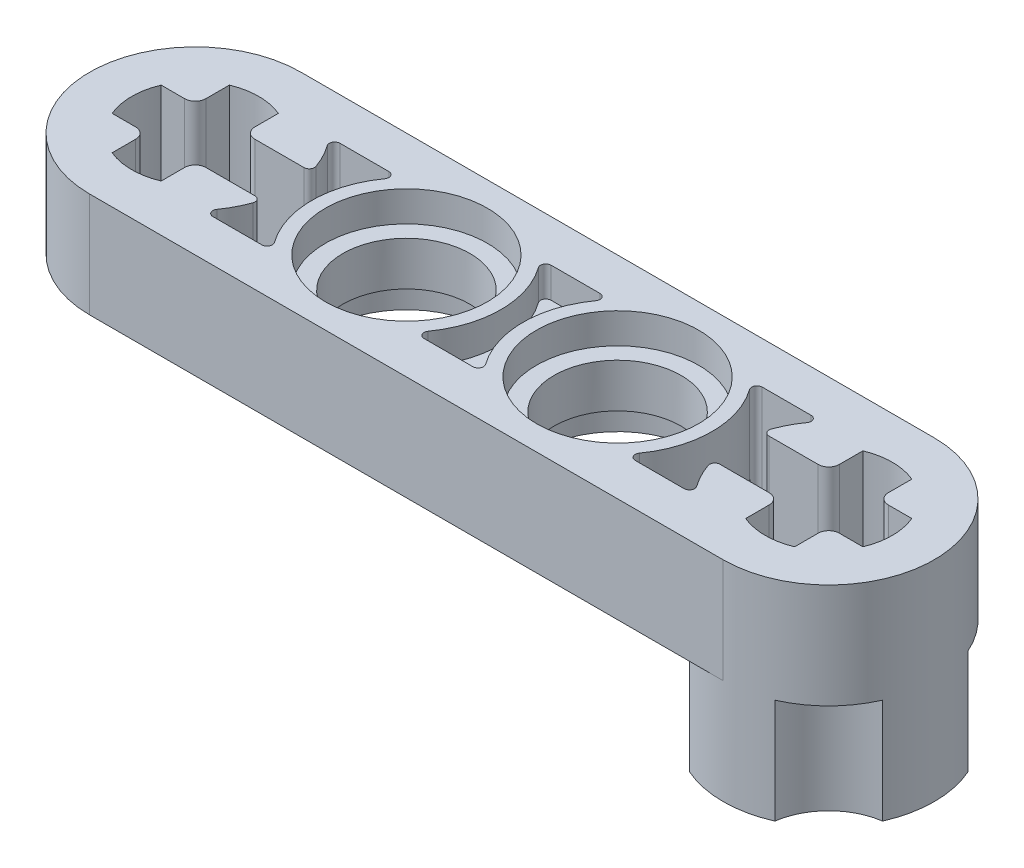
SolidWorks part; units mm, degrees
ref_plane "Front" through (0, 0, 0) normal (0, 0, 1) x (1, 0, 0)
ref_plane "Top" through (0, 0, 0) normal (0, 1, 0) x (1, 0, 0)
ref_plane "Right" through (0, 0, 0) normal (1, 0, 0) x (0, 0, -1)
sketch "Sketch1" plane through (0, 0, 0) normal (0, 1, 0) x (1, 0, 0)
  line L0 (0, 0) -> (0, 8.6394) construction
  line L1 (-11.9063, 3.9687) -> (11.9063, 3.9687)
  line L2 (11.9063, -3.9687) -> (-11.9063, -3.9687)
  line L3 (0, 0) -> (18.7139, 0) construction
  arc A0 (11.9063, 3.9687) -> (11.9063, -3.9687) centre (11.9063, 0) cw
  arc A1 (-11.9063, 3.9687) -> (-11.9063, -3.9687) centre (-11.9063, 0) ccw
  point P6 (0, 3.9687)
  point P11 (0, -3.9688)
  dimension "D1" = 7.9375
  dimension "D2" = 31.75
extrude "Base-Extrude" add sketch "Sketch1" along normal mid plane 3.937
sketch "Sketch2" plane through (0, 1.9685, 0) normal (0, 1, 0) x (-1, 0, 0)
  circle A0 centre (3.9688, 0) radius 2.3876
  dimension "D1" = 4.7752
  dimension "D2" = 3.9688
extrude "Cut-Extrude1" cut sketch "Sketch2" against normal through all
sketch "Sketch3" plane through (0, 1.9685, 0) normal (0, 1, 0) x (-1, 0, 0)
  circle A0 centre (3.9688, 0) radius 3.048
  dimension "D1" = 6.096
extrude "Cut-Extrude2" cut sketch "Sketch3" against normal blind 1.143
sketch "Sketch4" plane through (0, -1.9685, 0) normal (0, -1, 0) x (1, 0, 0)
  circle A0 centre (-3.9688, 0) radius 3.048
  dimension "D1" = 6.096
extrude "Cut-Extrude3" cut sketch "Sketch4" against normal blind 1.143
pattern_linear "LPattern1" count 2 spacing 7.9375 along (1, 0, 0) of "Cut-Extrude3", "Cut-Extrude2", "Cut-Extrude1"
sketch "Sketch5" plane through (0, 1.9685, 0) normal (0, 1, 0) x (-1, 0, 0)
  line L0 (11.9063, 0) -> (11.9063, -5.3472) construction
  line L1 (11.9063, 0) -> (8.2567, 0) construction
  line L2 (10.9855, -2.2029) -> (10.9855, -0.9207)
  line L3 (10.9855, -0.9207) -> (9.7033, -0.9207)
  line L4 (10.9855, 0.9208) -> (9.7033, 0.9208)
  line L5 (10.9855, 2.2029) -> (10.9855, 0.9208)
  line L6 (12.827, 2.2029) -> (12.827, 0.9208)
  line L7 (12.827, 0.9208) -> (14.1092, 0.9208)
  line L8 (12.827, -0.9207) -> (14.1092, -0.9207)
  line L9 (12.827, -2.2029) -> (12.827, -0.9207)
  arc A0 (10.9855, -2.2029) -> (12.827, -2.2029) centre (11.9063, 0) ccw
  arc A1 (9.7033, 0.9208) -> (9.7033, -0.9207) centre (11.9063, 0) ccw
  arc A2 (12.827, 2.2029) -> (10.9855, 2.2029) centre (11.9063, 0) ccw
  arc A3 (14.1092, -0.9207) -> (14.1092, 0.9208) centre (11.9063, 0) ccw
  dimension "D1" = 4.7752
  dimension "D2" = 0.9207
extrude "Cut-Extrude4" cut sketch "Sketch5" against normal through all
fillet "Fillet1" radius 0.3969 4 edges at (-12.827, 0, -0.9207) (-10.9855, 0, -0.9207) (-12.827, 0, 0.9208) (-10.9855, 0, 0.9208)
sketch "Sketch6" plane through (0, 1.9685, 0) normal (0, 1, 0) x (-1, 0, 0)
  line L0 (9.271, -2.3876) -> (6.604, -2.3876)
  line L1 (11.9063, 0) -> (3.9688, 0) construction
  line L2 (9.271, 2.3876) -> (6.604, 2.3876)
  line L3 (9.7033, -0.9207) -> (8.4715, -0.9207)
  line L4 (9.7033, 0.9208) -> (8.4715, 0.9208)
  circle A0 centre (3.9688, 0) radius 2.3876 construction
  arc A2 (6.604, -2.3876) -> (6.604, 2.3876) centre (3.9688, 0) ccw
  arc A3 (9.271, 2.3876) -> (8.4715, 0.9208) centre (11.9063, 0) ccw
  arc A4 (9.7033, 0.9208) -> (9.7033, -0.9207) centre (11.9063, 0) ccw construction
  arc A5 (9.7033, 0.9208) -> (9.7033, -0.9207) centre (11.9063, 0) ccw
  arc A6 (8.4715, -0.9207) -> (9.271, -2.3876) centre (11.9063, 0) ccw
  dimension "D2" = 7.112
extrude "Cut-Extrude5" cut sketch "Sketch6" against normal through all
fillet "Fillet2" radius 0.1984 6 edges at (-6.604, 0, -2.3876) (-9.271, 0, 2.3876) (-6.604, 0, 2.3876) (-9.271, 0, -2.3876) (-8.4715, 0, -0.9207) (-8.4715, 0, 0.9208)
mirror "Mirror1" about plane through (0, 0, 0) normal (1, 0, 0) of "Fillet2", "Cut-Extrude5", "Fillet1", "Cut-Extrude4"
sketch "Sketch7" plane through (7.6266, 1.9685, -1.7506) normal (0, 1, 0) x (-1, 0, 0)
  line L0 (8.9601, -0.637) -> (6.2931, -0.637)
  line L1 (11.5954, 1.7506) -> (3.6579, 1.7506) construction
  line L2 (8.9601, 4.1382) -> (6.2931, 4.1382)
  circle A0 centre (11.5954, 1.7506) radius 2.3876 construction
  circle A1 centre (3.6579, 1.7506) radius 2.3876 construction
  arc A2 (6.2931, -0.637) -> (6.2931, 4.1382) centre (3.6579, 1.7506) ccw
  arc A3 (8.9601, 4.1382) -> (8.0394, 1.7506) centre (11.5954, 1.7506) ccw
  arc A6 (8.0394, 1.7506) -> (8.9601, -0.637) centre (11.5954, 1.7506) ccw
  dimension "D2" = 7.112
extrude "Cut-Extrude6" cut sketch "Sketch7" against normal blind 1.143
fillet "Fillet3" radius 0.1984 4 edges at (-1.3335, 1.397, -2.3876) (1.3335, 1.397, -2.3876) (-1.3335, 1.397, 2.3876) (1.3335, 1.397, 2.3876)
mirror "Mirror2" about plane through (0, 0, 0) normal (0, 1, 0) of "Fillet3", "Cut-Extrude6"
sketch "Sketch8" plane through (0, -1.9685, 0) normal (0, -1, 0) x (1, 0, 0)
  circle A0 centre (11.9063, 0) radius 3.9687
  circle A1 centre (11.9063, 0) radius 2.3876
extrude "Boss-Extrude1" add sketch "Sketch8" along normal blind 3.937
sketch "Sketch9" plane through (0, -5.9055, 0) normal (0, -1, 0) x (1, 0, 0)
  line L0 (11.9063, 0) -> (11.9063, -4.7829) construction
  line L1 (11.9063, 0) -> (15.8424, -3.9361) construction
  circle A0 centre (15.875, -3.9687) radius 2.3876
  dimension "D2" = 4.7752
  dimension "D1" = 45
  dimension "D3" = 3.9688
extrude "Cut-Extrude7" cut sketch "Sketch9" against normal up to surface (3.937 mm away)
pattern_circular "CirPattern1" count 4 every 90 about axis through (11.9063, 1.9685, 0) along (0, -1, 0) of "Cut-Extrude7"
